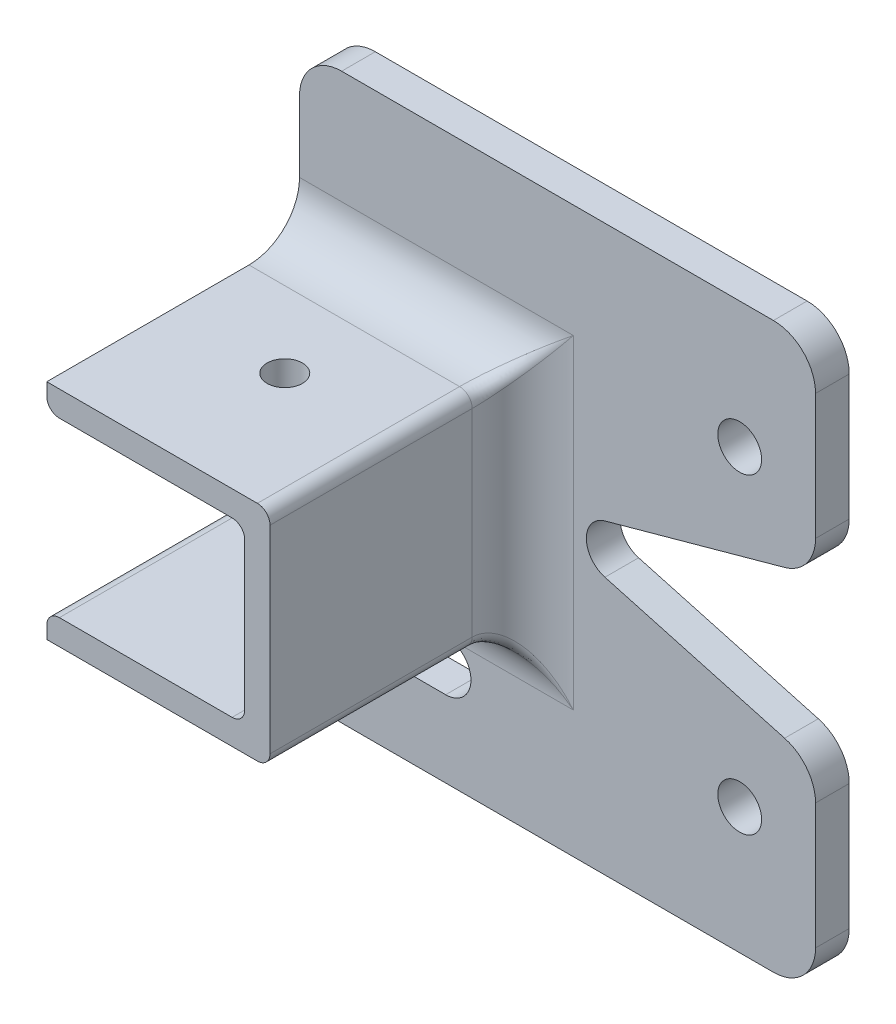
SolidWorks part; units mm, degrees
ref_plane "Front Plane" through (0, 0, 0) normal (0, 0, 1) x (1, 0, 0)
ref_plane "Top Plane" through (0, 0, 0) normal (0, 1, 0) x (1, 0, 0)
ref_plane "Right Plane" through (0, 0, 0) normal (1, 0, 0) x (0, 0, -1)
sketch "Sketch1" plane through (0, 0, 0) normal (0, 0, 1) x (1, 0, 0)
  line L0 (0, 0) -> (39, 0) construction
  line L1 (-10.25, 10.25) -> (10.25, 10.25)
  line L3 (-10.25, -10.25) -> (10.25, -10.25)
  line L4 (10.25, 10.25) -> (10.25, -10.25)
  line L5 (-10.25, 10.25) -> (10.25, -10.25) construction
  line L6 (-10.25, -10.25) -> (10.25, 10.25) construction
  line L7 (39, 0) -> (39, -0.83) construction
  line L8 (39, -0.83) -> (39, -19.33) construction
  line L9 (39, -0.83) -> (39, 17.67) construction
  line L11 (-13.25, -34.33) -> (48, -34.33)
  line L12 (48, -34.33) -> (48, 32.67)
  line L13 (48, 32.67) -> (-13.25, 32.67)
  line L14 (13.25, 13.25) -> (13.25, -13.25)
  line L15 (-13.25, -13.25) -> (13.25, -13.25)
  line L17 (-13.25, 13.25) -> (13.25, 13.25)
  line L18 (-13.25, 13.25) -> (-13.25, -13.25) construction
  line L19 (-10.25, 10.25) -> (-10.25, -10.25) construction
  line L20 (-13.25, 32.67) -> (-13.25, 10.25)
  line L21 (-10.25, -10.25) -> (-13.25, -10.25)
  line L22 (-10.25, 10.25) -> (-13.25, 10.25)
  line L23 (-13.25, -10.25) -> (-13.25, -34.33)
  circle A0 centre (39, 17.67) radius 2.6
  circle A1 centre (39, -19.33) radius 2.6
  point P0 (0, 0)
  dimension "D7" = 5.2
  dimension "D8" = 5.2
  dimension "D11" = 15
  dimension "D12" = 9
  dimension "D1" = 20.5
  dimension "D2" = 20.5
  dimension "D3" = 39
  dimension "D4" = 0.83
  dimension "D5" = 18.5
  dimension "D6" = 18.5
  dimension "D9" = 3
  dimension "D10" = 15
extrude "Boss-Extrude2" add sketch "Sketch1" along normal blind 4 contours A0 | A1 | L11 L12 L13 L20 L22 L1 L4 L3 L21 L23
sketch "Sketch2" plane through (0, 0, 4) normal (0, 0, 1) x (1, 0, 0)
  line L0 (-10.25, 10.25) -> (10.25, 10.25)
  line L1 (-10.25, -10.25) -> (10.25, -10.25)
  line L2 (10.25, 10.25) -> (10.25, -10.25)
  line L3 (13.25, 13.25) -> (13.25, -13.25)
  line L4 (-13.25, -13.25) -> (13.25, -13.25)
  line L5 (-13.25, 13.25) -> (13.25, 13.25)
  line L6 (-13.25, 13.25) -> (-13.25, 10.25)
  line L7 (-10.25, 10.25) -> (-13.25, 10.25)
  line L8 (-10.25, -10.25) -> (-13.25, -10.25)
  line L9 (-13.25, -10.25) -> (10.25, 10.25) construction
  line L10 (-13.25, 10.25) -> (10.25, -10.25) construction
  line L11 (-13.25, 32.67) -> (-13.25, 10.25) construction
  line L12 (-13.25, -10.25) -> (-13.25, -13.25)
  dimension "D1" = 3
  dimension "D2" = 20.5
  dimension "D3" = 20.5
  dimension "D4" = 3
  dimension "D5" = 3
extrude "Boss-Extrude3" add sketch "Sketch2" along normal blind 30
sketch "Sketch3" plane through (0, -13.25, 0) normal (0, -1, 0) x (1, 0, 0)
  line L0 (-13.25, 19) -> (13.25, 19) construction
  line L3 (-13.25, 34) -> (-13.25, 4) construction
  line L4 (13.25, 34) -> (13.25, 4) construction
  circle A0 centre (0, 19) radius 2.1
  dimension "D1" = 4.2
extrude "Cut-Extrude1" cut sketch "Sketch3" against normal blind 30
sketch "Sketch4" plane through (0, 0, 4) normal (0, 0, 1) x (1, 0, 0)
  line L0 (48, -0.83) -> (12.516, -0.83) construction
  line L1 (48, -34.33) -> (48, 32.67) construction
  line L2 (23, 2.062) -> (48, 8.9582)
  line L3 (23, -3.722) -> (48, -10.6182)
  line L4 (48, 8.9582) -> (48, -10.6182)
  arc A0 (23, 2.062) -> (23, -3.722) centre (23.7977, -0.83) ccw
  dimension "D1" = 3
  dimension "D2" = 25
extrude "Cut-Extrude3" cut sketch "Sketch4" against normal blind 30
sketch "Sketch6" plane through (0, 0, 0) normal (0, 0, -1) x (-1, 0, 0)
  line L0 (-11.25, -23.45) -> (11.25, -23.45)
  line L1 (13.25, -18.25) -> (-10.25, -18.25) construction
  line L2 (-10.25, -13.25) -> (13.25, -13.25)
  line L3 (-10.25, -13.25) -> (13.25, -13.25) construction
  line L4 (13.25, -10.25) -> (13.25, -34.33) construction
  line L5 (-9.25, -15.05) -> (9.25, -15.05)
  line L6 (-9.25, -15.05) -> (-9.25, -21.45)
  line L7 (-9.25, -21.45) -> (9.25, -21.45)
  line L8 (9.25, -15.05) -> (9.25, -16.25)
  line L9 (-9.25, -15.05) -> (9.25, -21.45) construction
  line L10 (-9.25, -21.45) -> (9.25, -15.05) construction
  line L11 (11.25, -13.05) -> (11.25, -15.4387)
  line L12 (-11.25, -13.05) -> (11.25, -13.05)
  line L13 (-11.25, -13.05) -> (-11.25, -23.45)
  line L14 (9.25, -20.25) -> (13.25, -20.25)
  line L15 (9.25, -16.25) -> (13.25, -16.25)
  line L16 (11.25, -21.1513) -> (13.25, -21.1513)
  line L17 (11.25, -15.4387) -> (13.25, -15.4387)
  line L18 (13.25, -21.1513) -> (13.25, -20.25)
  line L19 (13.25, -16.25) -> (13.25, -15.4387)
  line L20 (9.25, -20.25) -> (9.25, -21.45)
  line L21 (11.25, -21.1513) -> (11.25, -23.45)
  line L22 (11.25, -13.05) -> (11.25, -23.45) construction
  line L24 (9.25, -15.05) -> (9.25, -21.45) construction
  point P6 (0, -18.25)
  dimension "D2" = 5
  dimension "D4" = 18.5
  dimension "D5" = 6.4
  dimension "D6" = 2
  dimension "D7" = 2
  dimension "D8" = 2
  dimension "D1" = 3
  dimension "D3" = 2
sketch "Sketch8" plane through (0, 0, 0) normal (0, 0, -1) x (-1, 0, 0)
  line L0 (-7.0964, -22.25) -> (13.25, -22.25) construction
  line L2 (-10.25, -10.25) -> (13.25, -10.25) construction
  line L3 (13.25, -19.25) -> (-7.0964, -19.25)
  line L4 (-7.0964, -19.25) -> (-7.0964, -25.25)
  line L5 (-7.0964, -25.25) -> (13.25, -25.25)
  line L6 (13.25, -10.25) -> (13.25, -34.33) construction
  line L7 (13.25, -19.25) -> (13.25, -25.25)
  dimension "D1" = 3
  dimension "D2" = 12
  dimension "D3" = 20.3464
extrude "Cut-Extrude5" cut sketch "Sketch8" against normal through all and the other way through all
fillet "Fillet1" radius 5 2 edges at (48, -10.6182, 2) (48, 8.9582, 2)
fillet "Fillet2" radius 5 4 edges at (-13.25, 32.67, 2) (-13.25, -34.33, 2) (48, 32.67, 2) (48, -34.33, 2)
fillet "Fillet3" radius 6 3 edges at (0, 13.25, 4) (13.25, 0, 4) (0, -13.25, 4)
fillet "Fillet4" radius 1.5 2 edges at (-13.25, -10.25, 17) (-13.25, 10.25, 17)
fillet "Fillet5" radius 1.5 2 edges at (10.25, -10.25, 17) (10.25, 10.25, 17)
fillet "Fillet6" radius 1.5 4 edges at (15.0074, 15.0074, 5.7574) (15.0074, -15.0074, 5.7574) (13.25, 13.25, 22) (13.25, -13.25, 22)
fillet "Fillet7" radius 3 2 edges at (7.0964, -25.25, 2) (7.0964, -19.25, 2)
